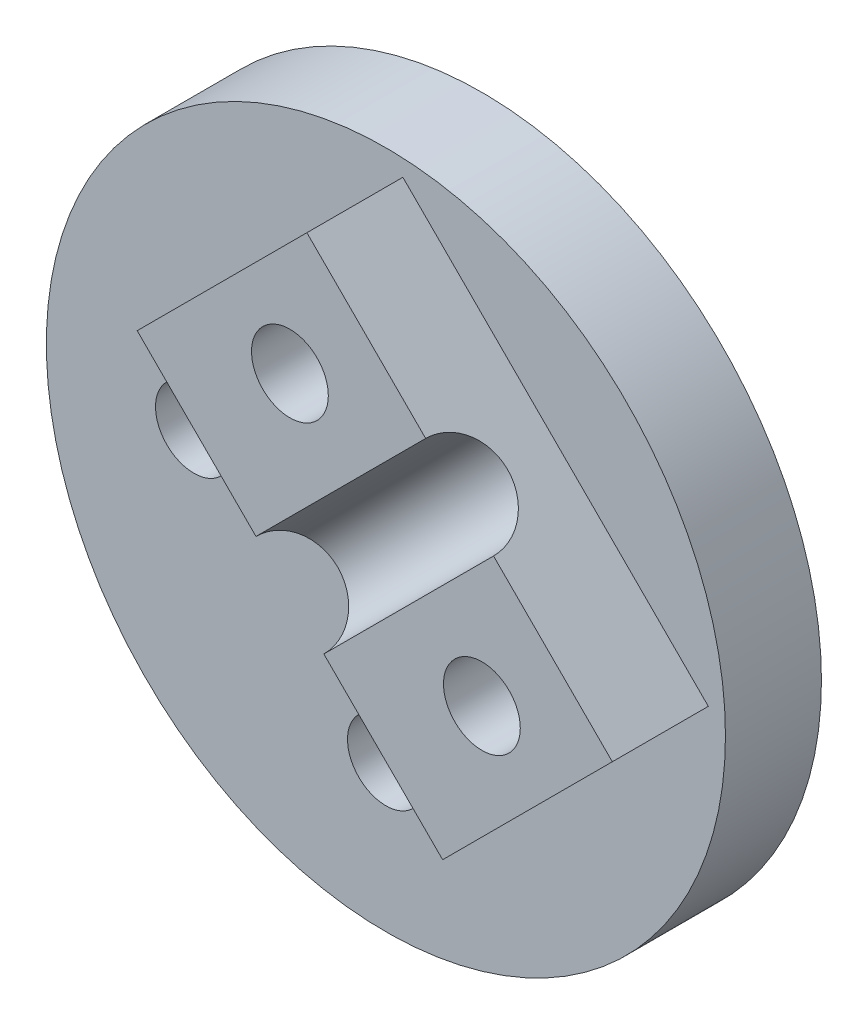
SolidWorks part; units mm, degrees
ref_plane "前视基准面" through (0, 0, 0) normal (0, 0, 1) x (1, 0, 0)
ref_plane "上视基准面" through (0, 0, 0) normal (0, 1, 0) x (1, 0, 0)
ref_plane "右视基准面" through (0, 0, 0) normal (1, 0, 0) x (0, 0, -1)
sketch "草图1" plane through (0, 0, 0) normal (0, 0, 1) x (1, 0, 0)
  circle A0 centre (0, 0) radius 14.1493
  circle A1 centre (0, -8) radius 1.6
  circle A2 centre (8, 0) radius 1.6
  circle A3 centre (0, 8) radius 1.6
  circle A4 centre (-8, 0) radius 1.6
  dimension "D1" = 3.2
  dimension "D2" = 3.2
  dimension "D3" = 3.2
  dimension "D4" = 3.2
extrude "凸台-拉伸1" add sketch "草图1" along normal blind 4
ref_axis "基准轴1" through (0, 0, 26.8028) along (0, 0, -1)
ref_plane "基准面4" through (0, 0, 0) normal (0.7071, 0.7071, 0) x (0, 0, -1)
sketch "草图3" plane through (0, 0, 0) normal (0.7071, 0.7071, 0) x (0, 0, -1)
  line L5 (-8, 2) -> (-8, -9)
  line L6 (-8, -9) -> (-4, -9)
  line L7 (-4, 14.1493) -> (-4, -14.1493) construction
  line L8 (-4, -9) -> (-4, 9)
  line L9 (-4, 9) -> (-8, 9)
  line L10 (-8, 9) -> (-8, 2)
  circle A0 centre (-8, 0) radius 2
  dimension "D3" = 0
  dimension "D4" = 4
  dimension "D1" = 9
  dimension "D2" = 9
extrude "凸台-拉伸2" add sketch "草图3" along normal blind 10 contours A0 L6 region at (0, 0, 5.8899)
sketch "草图4" plane through (0, 0, 8) normal (0, 0, 1) x (1, 0, 0)
  circle A0 centre (8, 0) radius 1.6
  circle A1 centre (0, 8) radius 1.6
  dimension "D1" = 3.2
  dimension "D2" = 3.2
extrude "切除-拉伸1" cut sketch "草图4" against normal blind 10
